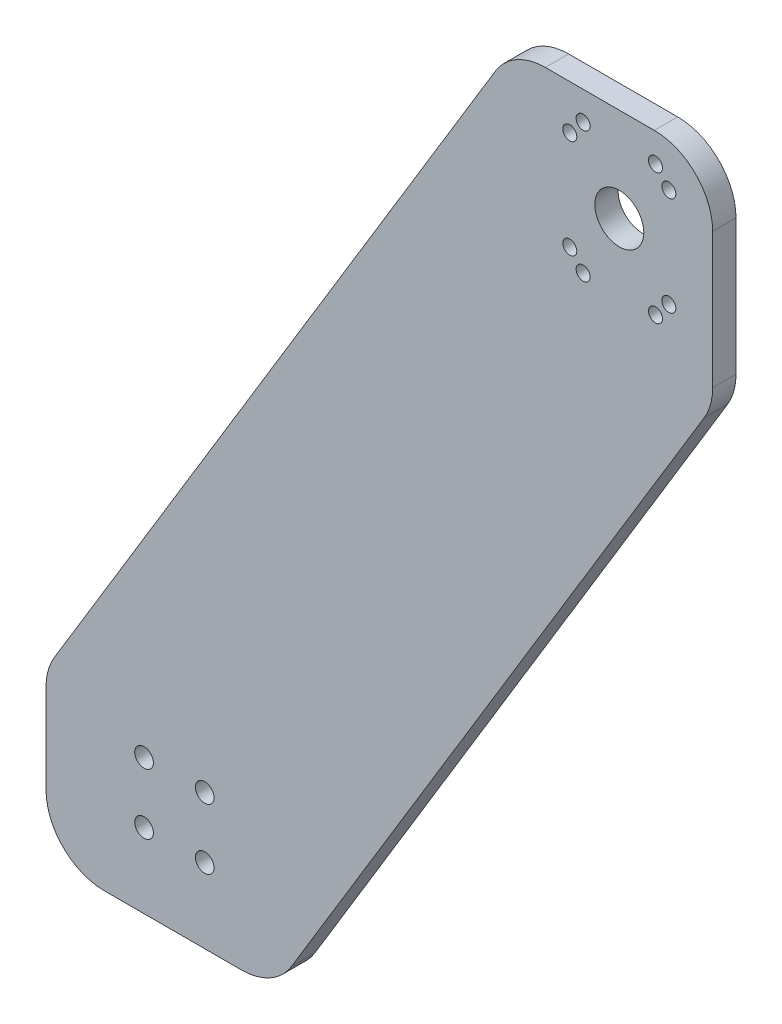
SolidWorks part; units mm, degrees
ref_plane "Piano frontale" through (0, 0, 0) normal (0, 0, 1) x (1, 0, 0)
ref_plane "Piano superiore" through (0, 0, 0) normal (0, 1, 0) x (1, 0, 0)
ref_plane "Piano destro" through (0, 0, 0) normal (1, 0, 0) x (0, 0, -1)
sketch "Schizzo1" plane through (0, 0, 0) normal (0, 0, 1) x (1, 0, 0)
  line L0 (25, 0) -> (83.8108, 0)
  line L1 (105.1949, 12.0493) -> (282.0244, 304.0295)
  line L2 (285.6403, 316.9801) -> (285.6403, 375)
  line L3 (260.6403, 400) -> (213.9419, 400)
  line L4 (0, 63.0199) -> (0, 25)
  line L5 (192.5578, 387.9507) -> (3.6159, 75.9705)
  line L6 (267.7327, 396.2552) -> (-16.2489, -72.6542) construction
  line L7 (14.2246, 45) -> (110.524, 45) construction
  line L8 (55.005, 45) -> (55.005, 90.084) construction
  line L9 (245.6403, 359.7762) -> (217.1497, 388.2668) construction
  line L10 (245.6403, 359.7762) -> (207.2912, 359.7762) construction
  line L11 (245.6403, 359.7762) -> (245.6403, 402.6918) construction
  line L13 (261.1403, 331.7762) -> (230.1403, 331.7762) construction
  line L14 (261.1403, 331.7762) -> (261.1403, 387.7762) construction
  line L15 (261.1403, 387.7762) -> (230.1403, 387.7762) construction
  line L16 (230.1403, 331.7762) -> (230.1403, 387.7762) construction
  line L17 (261.1403, 331.7762) -> (230.1403, 387.7762) construction
  line L18 (261.1403, 387.7762) -> (230.1403, 331.7762) construction
  circle A0 centre (42.005, 58) radius 4
  circle A1 centre (68.005, 58) radius 4
  circle A2 centre (68.005, 32) radius 4
  circle A3 centre (42.005, 32) radius 4
  circle A4 centre (245.6403, 359.7762) radius 10.5
  circle A5 centre (245.6403, 359.7762) radius 30 construction
  arc A6 (105.1949, 12.0493) -> (83.8108, 0) centre (83.8108, 25) cw
  arc A7 (25, 0) -> (0, 25) centre (25, 25) cw
  arc A8 (0, 63.0199) -> (3.6159, 75.9705) centre (25, 63.0199) cw
  arc A9 (285.6403, 316.9801) -> (282.0244, 304.0295) centre (260.6403, 316.9801) cw
  arc A10 (285.6403, 375) -> (260.6403, 400) centre (260.6403, 375) ccw
  arc A11 (213.9419, 400) -> (192.5578, 387.9507) centre (213.9419, 375) ccw
  circle A12 centre (230.1403, 387.7762) radius 3
  circle A13 centre (261.1403, 387.7762) radius 3
  circle A14 centre (266.8535, 380.9894) radius 3
  circle A15 centre (266.8535, 338.563) radius 3
  circle A16 centre (261.1403, 331.7762) radius 3
  circle A17 centre (230.1403, 331.7762) radius 3
  circle A18 centre (224.4271, 338.563) radius 3
  circle A19 centre (224.4271, 380.9894) radius 3
  point P27 (224.4271, 380.9894)
  point P28 (266.8535, 380.9894)
  point P29 (266.8535, 338.563)
  point P30 (224.4271, 338.563)
  point P39 (0, 0)
  point P42 (0, 70)
  point P45 (285.6403, 310)
  point P48 (285.6403, 400)
  dimension "D6" = 8
  dimension "D7" = 13
  dimension "D9" = 21
  dimension "D11" = 45
  dimension "D14" = 25
  dimension "D15" = 6
  dimension "D16" = 45
  dimension "D17" = 60
  dimension "D1" = 121.2
  dimension "D2" = 120
  dimension "D3" = 70
  dimension "D4" = 400
  dimension "D5" = 90
  dimension "D8" = 13
  dimension "D10" = 40
  dimension "D12" = 31
  dimension "D13" = 56
extrude "Estrusione-Estrusione2" add sketch "Schizzo1" against normal blind 10
sketch "Schizzo2" plane through (0, 0, 0) normal (0, -1, 0) x (1, 0, 0)
  line L0 (25, -5) -> (83.8108, -5) construction
  line L1 (25, -10) -> (25, 0) construction
  line L2 (83.8108, -10) -> (83.8108, 0) construction
  line L3 (54.4054, -5) -> (54.4054, 0) construction
  line L4 (25, 0) -> (83.8108, 0) construction
  circle A0 centre (54.4054, -5) radius 2
  circle A1 centre (81.9054, -5) radius 2
  circle A2 centre (26.9054, -5) radius 2
  dimension "D1" = 4
  dimension "D2" = 27.5
extrude "Taglio-Estrusione1" cut sketch "Schizzo2" against normal blind 15
